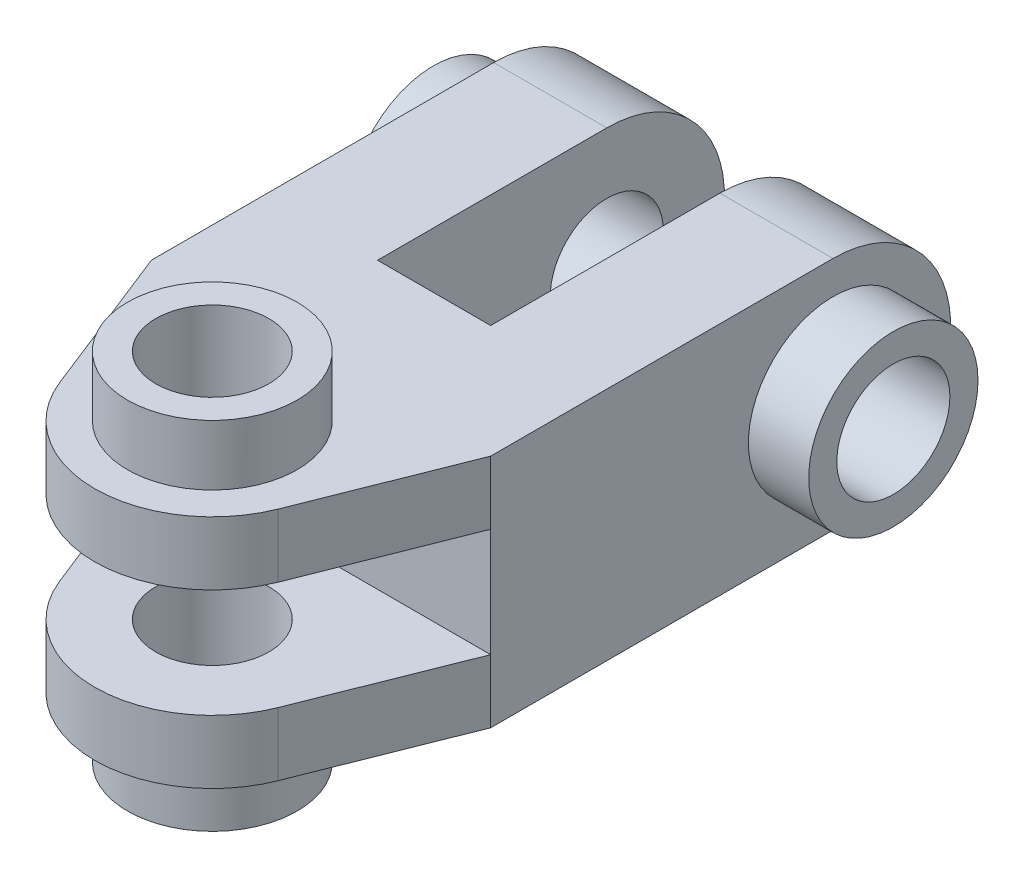
SolidWorks part; units mm, degrees
ref_plane "Front Plane" through (0, 0, 0) normal (0, 0, 1) x (1, 0, 0)
ref_plane "Top Plane" through (0, 0, 0) normal (0, 1, 0) x (1, 0, 0)
ref_plane "Right Plane" through (0, 0, 0) normal (1, 0, 0) x (0, 0, -1)
sketch "Sketch3" plane through (0, 0, 0) normal (1, 0, 0) x (0, 0, -1)
  line L0 (0, 19.812) -> (-57.658, 19.812)
  line L1 (0, -19.812) -> (-57.658, -19.812)
  line L2 (-57.658, 19.812) -> (-57.658, -19.812)
  line L3 (-57.658, 19.812) -> (-95.758, 19.812)
  line L4 (-95.758, 19.812) -> (-95.758, 9.144)
  line L5 (-95.758, 9.144) -> (-57.658, 9.144)
  line L6 (-57.658, 9.144) -> (-57.658, -19.812)
  line L7 (-95.758, -19.812) -> (-95.758, -9.144)
  line L8 (-95.758, -9.144) -> (-57.658, -9.144)
  line L9 (-95.758, -19.812) -> (-57.658, -19.812)
  arc A0 (0, -19.812) -> (0, 19.812) centre (0, 0) ccw
  dimension "D1" = 39.624
  dimension "D2" = 77.47
  dimension "D3" = 18.288
  dimension "D4" = 38.1
extrude "Boss-Extrude1" add sketch "Sketch3" along normal mid plane 57.15 contours L1 A0 L0 L2 L6 | L4 L5 L2 L3 | L7 L9 L6 L8 region at (0, 0, 20.9153) region at (0, 14.478, 76.708) region at (0, -14.478, 76.708)
sketch "Sketch4" plane through (0, 19.812, 0) normal (0, 1, 0) x (1, 0, 0)
  line L0 (28.575, 19.812) -> (-28.575, 19.812) construction
  line L1 (-9.525, 19.812) -> (9.525, 19.812)
  line L2 (-9.525, 19.812) -> (-9.525, -38.608)
  line L3 (-9.525, -38.608) -> (9.525, -38.608)
  line L4 (9.525, 19.812) -> (9.525, -38.608)
  line L5 (-28.575, 0) -> (-28.575, -95.758) construction
  line L6 (28.575, 0) -> (28.575, -95.758) construction
  line L7 (28.575, -95.758) -> (-28.575, -95.758) construction
  line L9 (-28.575, -57.658) -> (-18.4336, -83.2458)
  line L10 (28.575, -57.658) -> (18.3951, -83.265)
  line L11 (-28.575, -57.658) -> (28.575, -57.658)
  line L12 (-28.575, -57.658) -> (-28.575, -95.758)
  line L13 (-28.575, -95.758) -> (28.575, -95.758)
  line L14 (28.575, -57.658) -> (28.575, -95.758)
  arc A0 (-18.4336, -83.2458) -> (18.3951, -83.265) centre (-0.0154, -75.946) ccw
  circle A1 centre (-0.0154, -75.946) radius 9.525
  point P19 (0, -38.608)
  line M9 (-28.575, 0) -> (-28.575, -95.758)
  line M10 (-28.575, -95.758) -> (28.575, -95.758)
  line M11 (28.575, -95.758) -> (28.575, 0)
  line M12 (28.575, 0) -> (-28.575, 0)
  dimension "D4" = 39.624
  dimension "D7" = 19.05
  dimension "D1" = 19.05
  dimension "D2" = 19.05
  dimension "D3" = 58.42
  dimension "D5" = 28.5904
  dimension "D6" = 19.05
extrude "Cut-Extrude1" cut sketch "Sketch4" against normal through all contours L4 L2 L3 M12 | L4 L1 L2 M12 | A0 L13 L10 M11 | A1 | A0 L9 M9 M10 region at (0, 19.812, -9.906) region at (0, 19.812, 19.304) region at (-22.3383, 19.812, 84.0747) region at (22.3268, 19.812, 84.0697) region at (-0.0154, 19.812, 75.946)
sketch "Sketch5" plane through (0, 19.812, 0) normal (0, 1, 0) x (1, 0, 0)
  circle A0 centre (-0.0154, -75.946) radius 14.2875
  circle A1 centre (-0.0154, -75.946) radius 9.525
  dimension "D1" = 19.05
  dimension "D2" = 28.575
extrude "Boss-Extrude2" add sketch "Sketch5" along normal blind 10.16
extrude "Boss-Extrude3" add sketch "Sketch5<3>" against normal blind 10.16 from surface starting at face at (-0.0154, -19.812, 85.471)
sketch "Sketch5<3>" plane through (0, 19.812, 0) normal (0, 1, 0) x (1, 0, 0) same geometry as "Sketch5"
sketch "Sketch6" plane through (28.575, 0, 0) normal (1, 0, 0) x (0, 0, -1)
  circle A0 centre (0, 0) radius 9.525
  dimension "D1" = 19.05
extrude "Cut-Extrude2" cut sketch "Sketch6" against normal through all
sketch "Sketch7" plane through (28.575, 0, 0) normal (1, 0, 0) x (0, 0, -1)
  circle A0 centre (0, 0) radius 9.525
  circle A1 centre (0, 0) radius 14.2558
  dimension "D1" = 28.5115
  dimension "D2" = 19.05
extrude "Boss-Extrude4" add sketch "Sketch7" along normal blind 10.16
extrude "Boss-Extrude5" add sketch "Sketch7<2>" against normal blind 10.16 from surface starting at face at (-28.575, 0, -9.525)
sketch "Sketch7<2>" plane through (28.575, 0, 0) normal (1, 0, 0) x (0, 0, -1) same geometry as "Sketch7"
